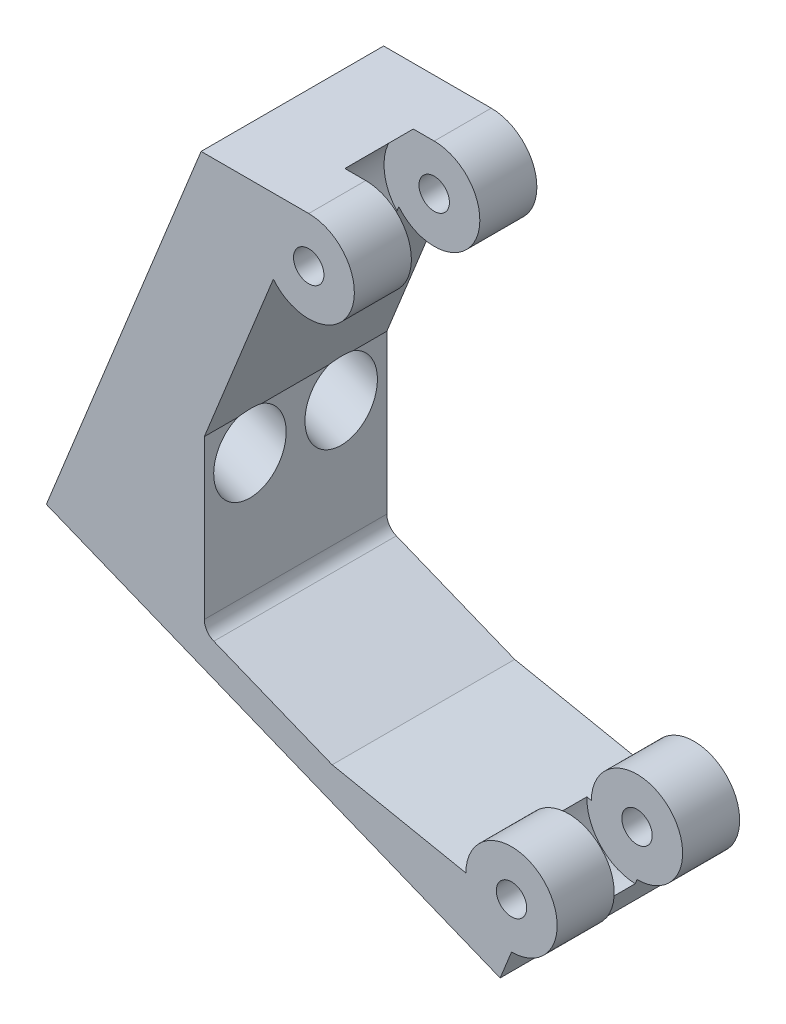
SolidWorks part; units mm, degrees
other "Markup1"
sketch "Sketch3" plane through (0, 0, 12) normal (0, 0, 1) x (1, 0, 0)
other "DetailItem1"
other "DetailItem3"
other "DetailItem5"
ref_plane "Front Plane" through (0, 0, 0) normal (0, 0, 1) x (1, 0, 0)
ref_plane "Top Plane" through (0, 0, 0) normal (0, 1, 0) x (1, 0, 0)
ref_plane "Right Plane" through (0, 0, 0) normal (1, 0, 0) x (0, 0, -1)
sketch "Sketch1" plane through (0, 0, 0) normal (0, 0, 1) x (1, 0, 0)
  line L2 (0, 6.6407) -> (0, 35.2105)
  line L3 (0, 35.2105) -> (8.8654, 35.2105)
  line L5 (6.5411, 30.3139) -> (2, 19.0743)
  line L6 (2, 19.0743) -> (2, 7.9897)
  line L7 (10.4069, 4.5931) -> (19.1992, 2.8287)
  line L11 (8.8654, 32.2105) -> (22.1992, 2.8287) construction
  line L15 (8.8654, 32.2105) -> (8.8654, 4.9405) construction
  line L16 (8.8654, 4.9405) -> (22.1992, 2.8287) construction
  line L17 (8.8654, 4.9405) -> (8.8654, -11.9834) construction
  line L21 (2, 7.9897) -> (10.4069, 4.5931)
  line L22 (-988.4786, -0.1713) -> (16.8603, -0.1713) construction
  line L23 (0, 6.6407) -> (21.45, -2.0257)
  line L24 (-905.7338, 372.5809) -> (46380.6427, -18732.3554) construction
  line L25 (22.1992, -0.1713) -> (50022.1992, -0.1713) construction
  line L26 (22.1992, -0.1713) -> (21.45, -2.0257)
  line L27 (-904.9846, 374.4353) -> (46381.392, -18730.501) construction
  line L28 (0.4221, 6.4701) -> (-46358.7706, 18736.7998) construction
  line L29 (2, 19.0743) -> (18732.3297, 46378.267) construction
  arc A0 (22.1992, -0.1713) -> (19.1992, 2.8287) centre (22.1992, 2.8287) ccw
  arc A1 (8.8654, 35.2105) -> (6.5411, 30.3139) centre (8.8654, 32.2105) cw
  circle A2 centre (8.8654, 32.2105) radius 1
  circle A3 centre (22.1992, 2.8287) radius 1
  point P2 (0, 0)
  dimension "D1" = 2
  dimension "D3" = 3
  dimension "D4" = 27.27
  dimension "D5" = 13.5
  dimension "D8" = 81
  dimension "D12" = 22
  dimension "D2" = 2
  dimension "D9" = 90
  dimension "D13" = 2
extrude "Boss-Extrude1" add sketch "Sketch1" along normal blind 12
ref_plane "midplane" through (0, 0, 6) normal (0, 0, 1) x (1, 0, 0)
sketch "Sketch2" plane through (0, 0, 6) normal (0, 0, 1) x (1, 0, 0)
  circle A0 centre (8.8654, 32.2105) radius 3.3
  circle A1 centre (22.1992, 2.8287) radius 3.3
  dimension "D1" = 6.6
extrude "Cut-Extrude1" cut sketch "Sketch2" against normal blind 2.25 and the other way blind 2.25
fillet "Fillet3" radius 1 1 edges at (2, 7.9897, 6)
ref_plane "Plane - base" through (-12.2296, 4.9411, 0) normal (-0.9272, 0.3746, 0) x (0, 0, -1)
sketch "Sketch4" plane through (-12.2296, 4.9411, 0) normal (-0.9272, 0.3746, 0) x (0, 0, -1)
  line L1 (-12, -32.6466) -> (0, -32.6466)
  line L2 (-12, -32.6466) -> (-12, -6.1571)
  line L3 (-12, -6.1571) -> (0, -6.1571)
  line L4 (0, -32.6466) -> (0, -6.1571)
  point P4 (0, 0)
  point P5 (0, 0)
  point P8 (0, 0)
extrude "Boss-Extrude2" add sketch "Sketch4" against normal up to surface up to face at (0, 20.9256, 6)
sketch "Hole sketch" plane through (7.6836, 33.1417, 0) normal (-0.9272, 0.3746, 0) x (0, 0, -1)
  line L0 (-12, 17.4202) -> (0, 17.4202) construction
  line L1 (-8.25, 3.3877) -> (-3.75, 3.3877) construction
  line L2 (0, 24.8243) -> (0, 15.1722) construction
  line L3 (-6, -1.7766) -> (-6, 49998.2234) construction
  line L4 (-6, 52.9241) -> (-6, 14.2895) construction
  line L5 (-12, 19.6681) -> (-12, 15.1722) construction
  line L6 (-12, 3.4206) -> (-12, 10.3547) construction
  line L7 (-12, 6.8877) -> (-6, 6.8877) construction
  circle A0 centre (-9, 17.4202) radius 1.2884
  circle A1 centre (-3, 17.4202) radius 1.2884
  circle A2 centre (-6, 6.8877) radius 1.2884
  point P8 (-9, 17.4202)
  point P9 (-3, 17.4202)
  point P10 (-6, 6.8877)
  dimension "D2" = 2.5768
  dimension "D1" = 3
  dimension "D3" = 3.5
extrude "Screw shaft holes" cut sketch "Hole sketch" against normal through all both and the other way through all
sketch "Sketch5" plane through (-4.9057, 1.982, 0) normal (0.9272, -0.3746, 0) x (0, 0, -1)
  circle A0 centre (-6, 26.7191) radius 2.3813
  circle A1 centre (-9, 16.1866) radius 2.3813
  circle A2 centre (-3, 16.1866) radius 2.3813
  dimension "D1" = 4.7625
extrude "Screw counterbores" cut sketch "Sketch5" against normal blind 2.5918 and the other way blind 5
sketch "Sketch6" plane through (-12.2296, 4.9411, 0) normal (-0.9272, 0.3746, 0) x (0, 0, 1)
  line L1 (-3.4001, 37.7488) -> (15.3252, 37.7488)
  line L2 (-3.4001, 37.7488) -> (-3.4001, 2.6951)
  line L3 (-3.4001, 2.6951) -> (15.3252, 2.6951)
  line L4 (15.3252, 37.7488) -> (15.3252, 2.6951)
extrude "Cut-Extrude2" cut sketch "Sketch6" against normal blind 1.66
equation "\"axle-diameter\"=2"
equation "\"D1@Sketch1\"=\"axle-diameter\""
equation "\"switch-thickness\"=12"
equation "\"D1@Boss-Extrude1\"=\"switch-thickness\""
equation "\"base-width\"=4.0"
equation "\"axle-bushing-radius\"=3"
equation "\"D3@Sketch1\"= \"axle-bushing-radius\""
equation "\"D1@Sketch2\"=\"axle-bushing-radius\"*2.2"
equation "\"D1@Cut-Extrude1\"=\"switch-thickness\"/6+\"clearance\""
equation "\"D2@Cut-Extrude1\"=\"switch-thickness\"/6+\"clearance\""
equation "\"clearance\"= 0.25"
equation "\"arm-width\"=3.0"
equation "\"min-diameter\"=70"
